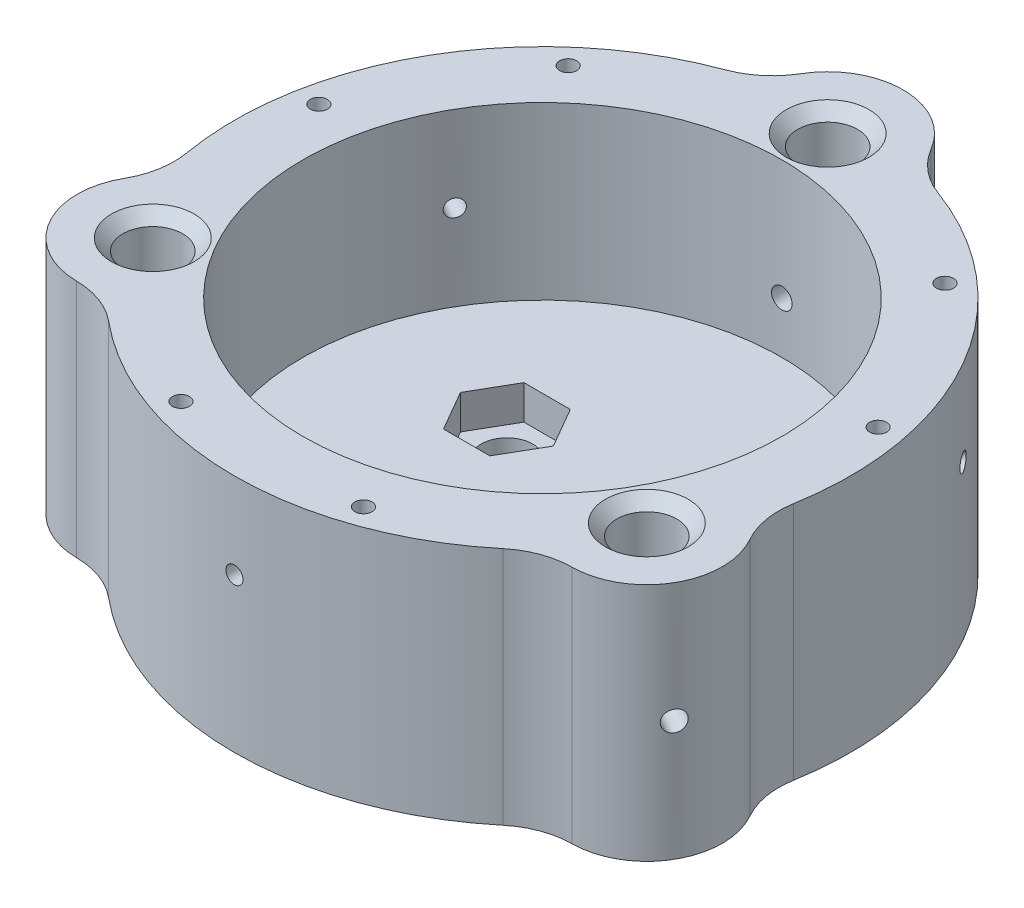
SolidWorks part; units mm, degrees
ref_plane "Спереди" through (0, 0, 0) normal (0, 0, 1) x (1, 0, 0)
ref_plane "Сверху" through (0, 0, 0) normal (0, 1, 0) x (1, 0, 0)
ref_plane "Справа" through (0, 0, 0) normal (1, 0, 0) x (0, 0, -1)
sketch "Эскиз1" plane through (0, 0, 0) normal (0, 1, 0) x (1, 0, 0)
  circle A0 centre (0, 0) radius 25 construction
  circle A1 centre (0, 25) radius 2.625
  circle A3 centre (0, 25) radius 6.625
  circle A4 centre (0, 0) radius 21
  circle A5 centre (0, 0) radius 27
  circle A6 centre (21.6506, -12.5) radius 6.625
  circle A7 centre (21.6506, -12.5) radius 2.625
  circle A8 centre (-21.6506, -12.5) radius 6.625
  circle A9 centre (-21.6506, -12.5) radius 2.625
  dimension "D1" = 50
  dimension "D2" = 5.25
  dimension "D3" = 4
  dimension "D5" = 4
  dimension "D4" = 2
  dimension "D6" = 3
extrude "Бобышка-Вытянуть1" add sketch "Эскиз1" along normal blind 15 contours A5 A3 A1 | A3 A5 A1 A4 | A6 A5 A3 A4 | A8 A4 A3 A5 | A7 A5 A6 A4 | A7 A5 A6 | A8 A5 A6 A4 | A9 A5 A8 | A9 A5 A8 A4 region at (2.5356, 0, -26.1215) region at (0, 0, -28.8173) region at (18.7892, 0, -10.848) region at (-18.7892, 0, -10.848) region at (-23.1574, 0, 6.2203) region at (-24.9565, 0, 14.4086) region at (24.9565, 0, 14.4086) region at (25.0266, 0, 9.6787) region at (0, 0, 21.6959)
sketch "Эскиз2" plane through (0, 0, 0) normal (0, -1, 0) x (1, 0, 0)
  arc A27 (25.9493, 7.4589) -> (19.4343, 18.7433) centre (21.6506, 12.5) ccw
  arc A28 (6.515, -26.2022) -> (25.9493, 7.4589) centre (0, 0) ccw
  arc A29 (-6.515, -26.2022) -> (6.515, -26.2022) centre (0, -25) ccw
  arc A30 (-25.9493, 7.4589) -> (-6.515, -26.2022) centre (0, 0) ccw
  arc A31 (-19.4343, 18.7433) -> (-25.9493, 7.4589) centre (-21.6506, 12.5) ccw
  arc A32 (19.4343, 18.7433) -> (-19.4343, 18.7433) centre (0, 0) ccw
  arc A33 (25.9493, 7.4589) -> (19.4343, 18.7433) centre (21.6506, 12.5) ccw
  arc A34 (6.515, -26.2022) -> (25.9493, 7.4589) centre (0, 0) ccw
  arc A35 (-6.515, -26.2022) -> (6.515, -26.2022) centre (0, -25) ccw
  arc A36 (-25.9493, 7.4589) -> (-6.515, -26.2022) centre (0, 0) ccw
  arc A37 (-19.4343, 18.7433) -> (-25.9493, 7.4589) centre (-21.6506, 12.5) ccw
  arc A38 (19.4343, 18.7433) -> (-19.4343, 18.7433) centre (0, 0) ccw
  dimension "D1" = 0
extrude "Бобышка-Вытянуть2" add sketch "Эскиз2" along normal blind 6
fillet "Скругление1" radius 7 6 edges at (6.515, 4.5, -26.2022) (-6.515, 4.5, -26.2022) (-25.9493, 4.5, 7.4589) (-19.4343, 4.5, 18.7433) (19.4343, 4.5, 18.7433) (25.9493, 4.5, 7.4589)
chamfer "Фаска1" distance 1 angle 45 3 edges at (0, 15, -22.375) (21.6506, 15, 15.125) (-21.6506, 15, 15.125)
sketch "Эскиз4" plane through (0, -6, 0) normal (0, -1, 0) x (1, 0, 0)
  circle A0 centre (0, 0) radius 8.5 construction
  circle A1 centre (0, 8.5) radius 2.25
  circle A2 centre (7.3612, -4.25) radius 2.25
  circle A3 centre (-7.3612, -4.25) radius 2.25
  dimension "D1" = 17
  dimension "D2" = 4.5
  dimension "D3" = 3
extrude "Вырез-Вытянуть1" cut sketch "Эскиз4" against normal through all
sketch "Эскиз5" plane through (0, 0, 0) normal (0, 1, 0) x (1, 0, 0)
  line L0 (2.0352, -12.025) -> (4.0703, -8.5)
  line L1 (5.3261, 0.725) -> (9.3964, 0.725)
  line L2 (9.3964, 0.725) -> (11.4315, 4.25)
  line L3 (11.4315, 4.25) -> (9.3964, 7.775)
  line L4 (9.3964, 7.775) -> (5.3261, 7.775)
  line L5 (5.3261, 7.775) -> (3.2909, 4.25)
  line L6 (3.2909, 4.25) -> (5.3261, 0.725)
  line L7 (4.0703, -8.5) -> (2.0352, -4.975)
  line L8 (2.0352, -4.975) -> (-2.0352, -4.975)
  line L9 (-2.0352, -4.975) -> (-4.0703, -8.5)
  line L10 (-4.0703, -8.5) -> (-2.0352, -12.025)
  line L11 (-2.0352, -12.025) -> (2.0352, -12.025)
  line L12 (-11.4315, 4.25) -> (-9.3964, 0.725)
  line L13 (-9.3964, 0.725) -> (-5.3261, 0.725)
  line L14 (-5.3261, 0.725) -> (-3.2909, 4.25)
  line L15 (-3.2909, 4.25) -> (-5.3261, 7.775)
  line L16 (-5.3261, 7.775) -> (-9.3964, 7.775)
  line L17 (-9.3964, 7.775) -> (-11.4315, 4.25)
  circle A2 centre (7.3612, 4.25) radius 3.525 construction
  circle A3 centre (0, -8.5) radius 3.525 construction
  circle A4 centre (-7.3612, 4.25) radius 3.525 construction
  circle A5 centre (0, -8.5) radius 2.25 construction
  dimension "D1" = 7.05
  dimension "D2" = 3
extrude "Вырез-Вытянуть2" cut sketch "Эскиз5" against normal blind 3
sketch "Эскиз6" plane through (0, 15, 0) normal (0, 1, 0) x (1, 0, 0)
  line L0 (0, 0) -> (0, -25) construction
  line L1 (-8, -23.6854) -> (8, -23.6854) construction
  circle A0 centre (0, 0) radius 25 construction
  circle A1 centre (-8, -23.6854) radius 0.75
  circle A2 centre (8, -23.6854) radius 0.75
  circle A3 centre (-16.5122, 18.7709) radius 0.75
  circle A4 centre (-24.5122, 4.9145) radius 0.75
  circle A5 centre (24.5122, 4.9145) radius 0.75
  circle A6 centre (16.5122, 18.7709) radius 0.75
  dimension "D2" = 1.5
  dimension "D3" = 1.5
  dimension "D1" = 16
  dimension "D4" = 3
extrude "Вырез-Вытянуть3" cut sketch "Эскиз6" against normal through all
sketch "Эскиз7" plane through (0, 0, 0) normal (0, 0, 1) x (1, 0, 0)
  line L0 (17.2802, 15) -> (-17.2802, 15) construction
  line L1 (0, 15) -> (0, 0) construction
  circle A0 centre (0, 7.5) radius 0.75
  dimension "D1" = 1.5
extrude "Вырез-Вытянуть4" cut sketch "Эскиз7" along normal through all
pattern_circular "Круговой массив1" count 3 over 360 about axis through (0, 15, 0) along (0, -1, 0) of "Вырез-Вытянуть4"
ref_plane "Плоскость1" through (0, 0, -31.625) normal (0, 0, -1) x (-1, 0, 0)
sketch "Эскиз8" plane through (0, 0, -31.625) normal (0, 0, -1) x (-1, 0, 0)
  line L0 (0, 15) -> (0, -6) construction
  line L1 (5.7106, 15) -> (-5.7106, 15) construction
  line L2 (-5.7106, -6) -> (5.7106, -6) construction
  circle A0 centre (0, 4.5) radius 0.9
  dimension "D1" = 1.8
extrude "Вырез-Вытянуть5" cut sketch "Эскиз8" against normal up to surface (10.6443 mm away) up to face at (17.8105, 7.672, -11.1259)
pattern_circular "Круговой массив2" count 3 over 360 about axis through (0, 15, 0) along (0, -1, 0) of "Вырез-Вытянуть5"
equation "\"motor_diameter\"= 30"
equation "\"mm_diameter\"= IIF ( \"motor_diameter\" < 34 , 41 , \"motor_diameter\" + 8 )"
equation "\"upper_shafts_diameter\"= 5"
equation "\"upper_shats_length\"= 180"
equation "\"upper_bearing_d1\"= 10"
equation "\"upper_bearing_d2\"= 5"
equation "\"upper_bearing_h\"= 15"
equation "\"lower_shafts_diameter\"= 5"
equation "\"lower_shafts_length\"= 180"
equation "\"lower_bearing_d1\"= 10"
equation "\"lower_bearing_d2\"= 5"
equation "\"lower_bearing_h\"= 15"
equation "\"print_offset\"= 0.5"
equation "\"bh_screws_d\"= 2"
equation "\"bh_screws_h\"= 20"
equation "\"bh_screws_hh_d\"= 3.4"
equation "\"bh_screws_hh_h\"= 2"
equation "\"bh_nut_d\"= 3.8"
equation "\"bh_nut_h\"= 2"
equation "\"motor_screws_d\"= 3"
equation "\"motor_screws_h\"= 16"
equation "\"motor_screws_hh_d\"= 5.5"
equation "\"motor_screws_hh_h\"= 3"
equation "\"plate_hole_distance\"= 25.4"
equation "\"plate_screws_d\"= 6.5"
equation "\"shafts_diameter\"= IIF ( \"mm_diameter\" < 42 , 42 + 8 , \"mm_diameter\" + 8 )"
equation "\"central_hole_diameter\"= 8"
equation "\"bh_thikness\"= 4"
equation "\"D1@Эскиз1\"=\"shafts_diameter\""
equation "\"D2@Эскиз1\" = \"upper_shafts_diameter\" + \"print_offset\" / 2"
equation "\"D3@Эскиз1\"=\"bh_thikness\""
equation "\"D1@Бобышка-Вытянуть1\"= \"upper_bearing_h\""
equation "\"D1@Бобышка-Вытянуть2\"=6"
equation "\"D4@Эскиз1\"=\"D3@Эскиз1\"/2"
equation "\"D2@Эскиз4\"=\"ends_screws_d\"+\"print_offset\""
equation "\"D1@Эскиз5\"=\"ends_nut_d\"+\"print_offset\"/2"
equation "\"D1@Вырез-Вытянуть2\"=\"ends_nut_h\""
equation "\"D5@Эскиз1\"=\"bh_thikness\""
equation "\"ends_screws_d\"= 4"
equation "\"ends_screws_h\"= 16"
equation "\"ends_screws_hh_d\"= 6.7"
equation "\"ends_screws_hh_h\"= 4.1"
equation "\"ends_nut_d\"= 6.8"
equation "\"ends_nut_h\"= 3"
equation "\"D2@Эскиз6\"=\"bh_screws_d\"-\"print_offset\""
equation "\"D3@Эскиз6\"=\"D2@Эскиз6\""
equation "\"D1@Эскиз7\"=\"bh_screws_d\"-\"print_offset\""
equation "\"D1@Эскиз8\"=\"bh_screws_d\"-0.2"
